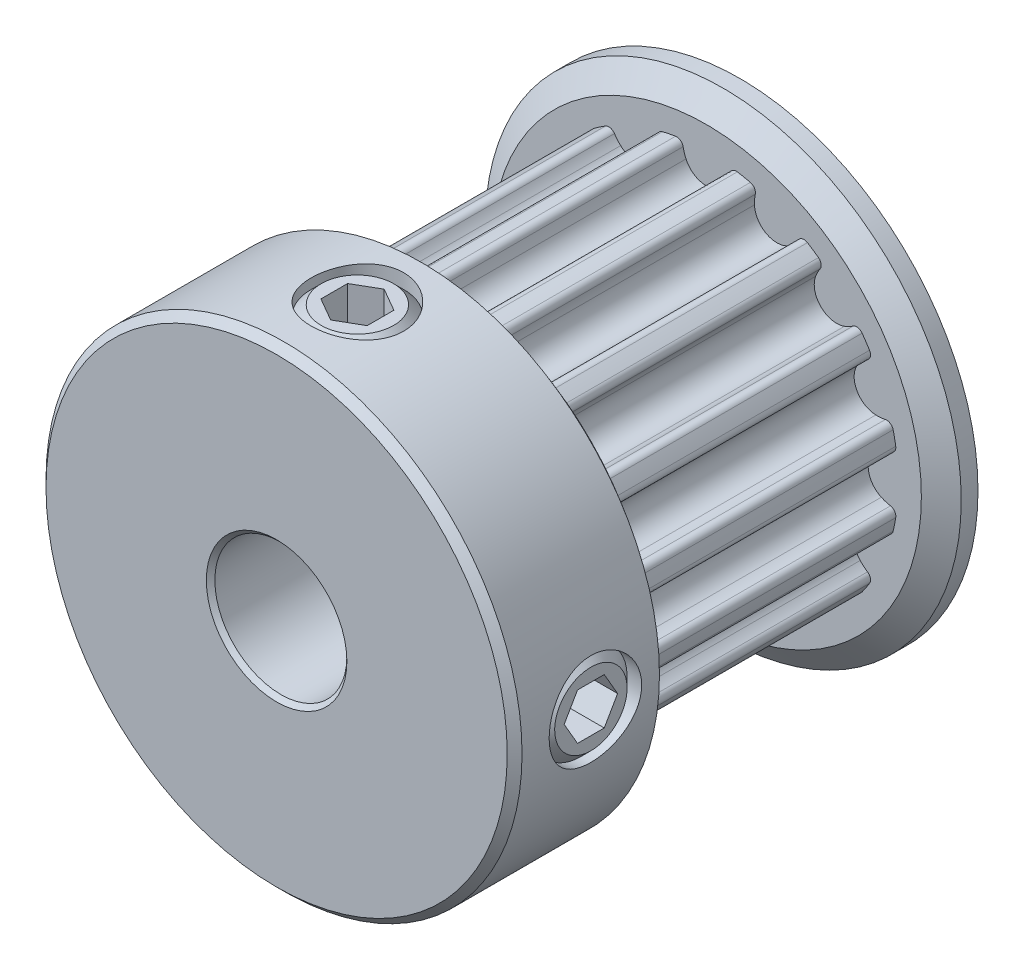
SolidWorks part; units mm, degrees
ref_plane "Front Plane" through (0, 0, 0) normal (0, 0, 1) x (1, 0, 0)
ref_plane "Top Plane" through (0, 0, 0) normal (0, 1, 0) x (1, 0, 0)
ref_plane "Right Plane" through (0, 0, 0) normal (1, 0, 0) x (0, 0, -1)
sketch "Sketch1" plane through (0, 0, 0) normal (0, 0, 1) x (1, 0, 0)
  line L1 (-2.553, 6.1245) -> (2.553, 6.1245) construction
  line L4 (0, 0) -> (0, 6.1245) construction
  line L5 (0, 6.1245) -> (0, 12.0266) construction
  line L6 (0, 7.6455) -> (2.9417, 7.0569) construction
  line L7 (2.9417, 7.0569) -> (3.8741, 6.6682) construction
  line L8 (2.9417, 7.0569) -> (2.553, 6.1245) construction
  line L9 (-2.9417, 7.0569) -> (-2.553, 6.1245) construction
  line L10 (-2.7951, 6.7052) -> (-3.7579, 9.015)
  line L11 (-3.7579, 9.015) -> (3.7579, 9.015)
  line L12 (3.7579, 9.015) -> (2.7951, 6.7052)
  circle A0 centre (0, 0) radius 7.6455 construction
  circle A1 centre (0, 0) radius 9.015 construction
  circle A2 centre (0, 0) radius 7.2645 construction
  arc A3 (-0.7739, 6.6229) -> (0.7739, 6.6229) centre (0, 6.9745) ccw
  arc A4 (-0.7739, 6.6229) -> (-0.8836, 6.9694) centre (0.61, 7.2516) cw
  arc A5 (-2.7951, 6.7052) -> (-1.1695, 7.1697) centre (0, 0) cw
  arc A6 (-0.8836, 6.9694) -> (-1.1695, 7.1697) centre (-1.1292, 6.923) ccw
  arc A7 (2.7951, 6.7052) -> (1.1695, 7.1697) centre (0, 0) ccw
  arc A8 (0.8836, 6.9694) -> (1.1695, 7.1697) centre (1.1292, 6.923) cw
  arc A9 (0.7739, 6.6229) -> (0.8836, 6.9694) centre (-0.61, 7.2516) ccw
  point P6 (0, 20.9083)
  point P11 (0, 7.6455)
  point P13 (0, 9.015)
  point P14 (0, 7.2645)
  dimension "D1" = 8.8817
  dimension "D2" = 4.3811
sketch "Sketch2" plane through (0, 0, 0) normal (1, 0, 0) x (0, 0, -1)
  line L0 (-8.775, 2.3812) -> (8.775, 2.3812)
  line L1 (-8.775, 2.3812) -> (-8.775, 9.015)
  line L2 (-3.29, 9.015) -> (-8.775, 9.015)
  line L3 (-3.925, 2.3813) -> (-3.925, 9.015) construction
  line L4 (-3.925, 9.015) -> (-2.655, 9.015) construction
  line L5 (-2.655, 9.015) -> (-2.655, 7.2645) construction
  line L6 (-2.655, 7.2645) -> (7.505, 7.2645)
  line L7 (7.505, 7.2645) -> (7.505, 9.015) construction
  line L8 (7.505, 9.015) -> (8.775, 9.015) construction
  line L9 (8.775, 9.015) -> (8.775, 2.3812)
  line L10 (-8.775, 0) -> (8.775, 0) construction
  line L11 (8.14, 9.015) -> (7.505, 8.1398)
  line L12 (-2.655, 8.1398) -> (-3.29, 9.015)
  line L14 (-2.655, 8.1398) -> (-2.655, 7.2645)
  line L15 (7.505, 7.2645) -> (7.505, 8.1398)
  line L16 (8.14, 9.015) -> (8.775, 9.015)
  arc A0 (-2.655, 8.1398) -> (-3.29, 9.015) centre (-3.5757, 8.1398) ccw construction
  arc A1 (7.505, 8.1398) -> (8.14, 9.015) centre (8.4257, 8.1398) cw construction
  point P12 (-2.655, 8.1398)
  point P14 (-3.29, 9.015)
  point P20 (7.505, 8.1398)
  point P21 (8.14, 9.015)
  point P25 (7.505, 0)
  point P26 (-2.655, 0)
  dimension "OA" = 17.55
  dimension "Bore" = 4.7625
  dimension "Outside Width" = 11.43
  dimension "Inside Width" = 10.16
revolve "Revolve1" add sketch "Sketch2" angle 360 mid plane about L10
sketch "Sketch3" plane through (0, 0, 0) normal (0, 0, 1) x (1, 0, 0)
  line L6 (3.7579, 9.015) -> (-3.7579, 9.015)
  line L7 (2.7951, 6.7052) -> (3.7579, 9.015)
  line L8 (-3.7579, 9.015) -> (-2.7951, 6.7052)
  line L9 (3.7579, 9.015) -> (-3.7579, 9.015)
  line L10 (2.7951, 6.7052) -> (3.7579, 9.015)
  line L11 (-3.7579, 9.015) -> (-2.7951, 6.7052)
  arc A8 (2.7951, 6.7052) -> (1.1695, 7.1697) centre (0, 0) ccw
  arc A9 (1.1695, 7.1697) -> (0.8836, 6.9694) centre (1.1292, 6.923) ccw
  arc A10 (0.7739, 6.6229) -> (0.8836, 6.9694) centre (-0.61, 7.2516) ccw
  arc A11 (-0.7739, 6.6229) -> (0.7739, 6.6229) centre (0, 6.9745) ccw
  arc A12 (-0.8836, 6.9694) -> (-0.7739, 6.6229) centre (0.61, 7.2516) ccw
  arc A13 (-0.8836, 6.9694) -> (-1.1695, 7.1697) centre (-1.1292, 6.923) ccw
  arc A14 (-1.1695, 7.1697) -> (-2.7951, 6.7052) centre (0, 0) ccw
  arc A15 (2.7951, 6.7052) -> (1.1695, 7.1697) centre (0, 0) ccw
  arc A16 (1.1695, 7.1697) -> (0.8836, 6.9694) centre (1.1292, 6.923) ccw
  arc A17 (0.7739, 6.6229) -> (0.8836, 6.9694) centre (-0.61, 7.2516) ccw
  arc A18 (-0.7739, 6.6229) -> (0.7739, 6.6229) centre (0, 6.9745) ccw
  arc A19 (-0.8836, 6.9694) -> (-0.7739, 6.6229) centre (0.61, 7.2516) ccw
  arc A20 (-0.8836, 6.9694) -> (-1.1695, 7.1697) centre (-1.1292, 6.923) ccw
  arc A21 (-1.1695, 7.1697) -> (-2.7951, 6.7052) centre (0, 0) ccw
  dimension "D1" = 0
extrude "Cut-Extrude1" cut sketch "Sketch3" against normal up to vertex (7.505 mm away) from vertex up to point (0, 7.2645, -7.505) starting at point (0, 7.2645, 2.655)
pattern_circular "CirPattern1" count 16 over 360 about axis through (0, 0, 8.775) along (0, 0, 1) of "Cut-Extrude1"
sketch "Sketch4" plane through (0, 0, 0) normal (1, 0, 0) x (0, -1, 0)
  line L0 (0, -2.655) -> (0, -8.775) construction
  line L1 (-2.3812, -8.775) -> (2.3812, -8.775) construction
  line L2 (8.1398, -2.655) -> (-8.1398, -2.655) construction
  circle A0 centre (0, -5.715) radius 1.7526
extrude "Cut-Extrude2" cut sketch "Sketch4" along normal through all
ref_plane "Plane1" through (0, 0, 5.715) normal (0, 0, 1) x (1, 0, 0)
sketch "Sketch5" plane through (0, 0, 5.715) normal (0, 0, 1) x (1, 0, 0)
  line L0 (0, 0) -> (0, 9.015) construction
  line L1 (2.3812, -1.3716) -> (2.3812, 0)
  line L2 (2.7622, -1.7526) -> (8.462, -1.7526)
  line L3 (2.3812, 0) -> (9.015, 0) construction
  line L4 (2.3812, 0) -> (8.843, 0)
  line L5 (8.843, 0) -> (8.843, -1.3716)
  line L6 (2.7622, -1.7526) -> (2.3812, -1.3716)
  line L7 (8.843, -1.3716) -> (8.462, -1.7526)
  circle A0 centre (0, 0) radius 9.015 construction
  circle A1 centre (0, 0) radius 2.3812 construction
  point P2 (2.3812, -1.7526)
  point P11 (8.843, -1.7526)
revolve "Revolve2" add sketch "Sketch5" angle 360 mid plane about L4
sketch "Sketch6" plane through (8.843, 5.3841, 0) normal (-1, 0, 0) x (0, -1, 0)
  line L1 (5.3841, 6.7269) -> (4.5078, 6.2209)
  line L2 (4.5078, 6.2209) -> (4.5078, 5.2091)
  line L3 (4.5078, 5.2091) -> (5.3841, 4.7031)
  line L4 (5.3841, 4.7031) -> (6.2604, 5.2091)
  line L5 (6.2604, 5.2091) -> (6.2604, 6.2209)
  line L6 (6.2604, 6.2209) -> (5.3841, 6.7269)
  circle A0 centre (5.3841, 5.715) radius 0.8763 construction
  dimension "D1" = 1.7526
extrude "Cut-Extrude3" cut sketch "Sketch6" along normal blind 1.3144
pattern_circular "CirPattern3" count 2 over 90 about axis through (0, 0, 8.775) along (0, 0, 1) of "Cut-Extrude2", "Revolve2", "Cut-Extrude3"
chamfer "Chamfer1" distance 0.2807 angle 45 2 edges at (2.3812, 0, 8.775) (9.015, 0, 8.775)
ref_axis "Center Axis 1" through (0, 0, -8.775) along (0, 0, 1)
ref_plane "Contact Plane 1" through (0, 0, 8.775) normal (0, 0, 1) x (1, 0, 0)
ref_plane "Contact Plane 2" through (0, 0, -8.775) normal (0, 0, -1) x (-1, 0, 0)
sketch "Sketch7" plane through (0, 0, -8.775) normal (0, 0, -1) x (-1, 0, 0)
  circle A0 centre (0, 0) radius 2.5
  dimension "D1" = 5
extrude "Cut-Extrude4" cut sketch "Sketch7" against normal through all
equation "\"D2@Sketch1\"= \"D1@Sketch1\" / 2"
equation "\"D1@Sketch6\" = \"Set Screw@Sketch4\" / 2"
equation "\"D1@Cut-Extrude3\" = \"D1@Sketch6\"*.75"
